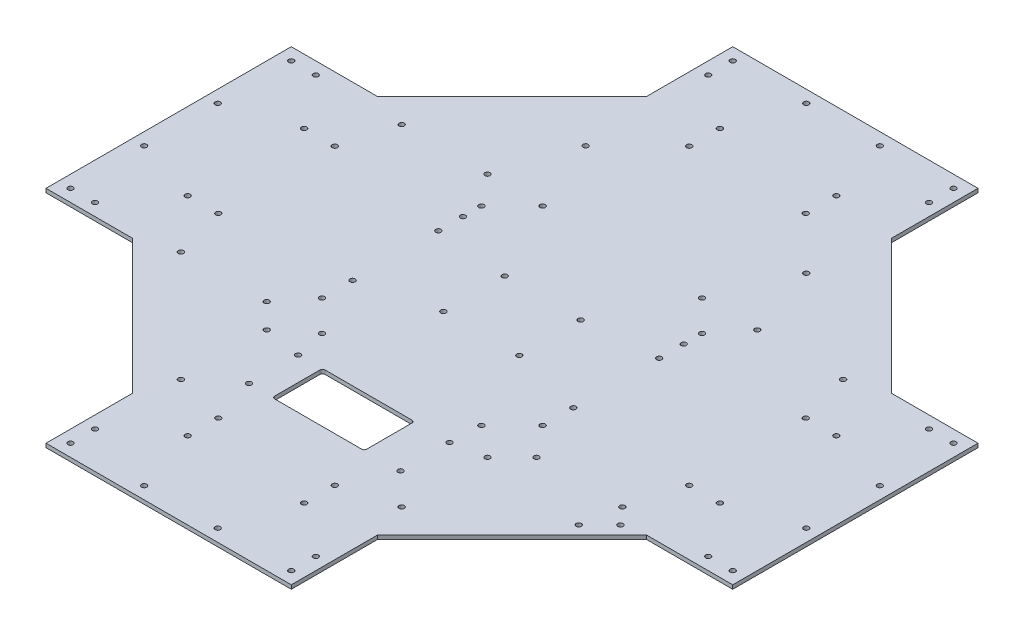
SolidWorks part; units mm, degrees
ref_plane "Front Plane" through (0, 0, 0) normal (0, 0, 1) x (1, 0, 0)
ref_plane "Top Plane" through (0, 0, 0) normal (0, 1, 0) x (1, 0, 0)
ref_plane "Right Plane" through (0, 0, 0) normal (1, 0, 0) x (0, 0, -1)
sketch "Sketch1" plane through (0, 0, 0) normal (0, 1, 0) x (1, 0, 0)
  line L0 (0, -280) -> (100, -280)
  line L1 (100, -280) -> (100, -209.6016)
  line L2 (280, -100) -> (209.6016, -100)
  line L3 (0, 0) -> (0, -280) construction
  line L4 (280, 0) -> (280, -100)
  line L5 (-280, 280) -> (280, 280) construction
  line L6 (-280, 280) -> (-280, -280) construction
  line L7 (-280, -280) -> (280, -280) construction
  line L8 (280, 280) -> (280, -280) construction
  line L9 (-280, 280) -> (280, -280) construction
  line L10 (-280, -280) -> (280, 280) construction
  line L11 (100, -209.6016) -> (209.6016, -100)
  line L12 (-280, 0) -> (-280, -100)
  line L13 (-280, -100) -> (-209.6016, -100)
  line L14 (-209.6016, -100) -> (-100, -209.6016)
  line L15 (-100, -280) -> (-100, -209.6016)
  line L16 (0, -280) -> (-100, -280)
  line L17 (0, 280) -> (-100, 280)
  line L18 (-100, 280) -> (-100, 209.6016)
  line L19 (-100, 209.6016) -> (-209.6016, 100)
  line L20 (-280, 100) -> (-209.6016, 100)
  line L21 (-280, 0) -> (-280, 100)
  line L22 (280, 0) -> (280, 100)
  line L23 (280, 100) -> (209.6016, 100)
  line L24 (209.6016, 100) -> (100, 209.6016)
  line L25 (100, 280) -> (100, 209.6016)
  line L26 (0, 280) -> (100, 280)
  line L27 (111.5258, -219.2889) -> (219.2889, -111.5258) construction
  line L28 (219.2889, -111.5258) -> (247.5732, -139.8101) construction
  line L29 (247.5732, -139.8101) -> (139.8101, -247.5732) construction
  line L30 (139.8101, -247.5732) -> (111.5258, -219.2889) construction
  line L31 (-100, -270) -> (100, -270) construction
  line L32 (-90, -280) -> (-90, 280) construction
  line L33 (-75, -75) -> (75, -75) construction
  line L34 (-75, -75) -> (-75, 75) construction
  line L35 (-75, 75) -> (75, 75) construction
  line L36 (75, -75) -> (75, 75) construction
  line L37 (-75, -75) -> (75, 75) construction
  line L38 (-75, 75) -> (75, -75) construction
  line L39 (-100, -260) -> (100, -260) construction
  line L40 (-280, 40) -> (280, 40) construction
  line L41 (0, 280) -> (0, 0) construction
  line L42 (-280, -90) -> (280, -90) construction
  line L43 (-260, -100) -> (-260, 100) construction
  line L44 (0, 0) -> (-280, 0) construction
  arc A0 (100, -280) -> (280, -100) centre (100, -100) ccw construction
  circle A1 centre (-47.5, -192) radius 2.125
  circle A2 centre (-47.5, -217) radius 2.125
  circle A3 centre (47.5, -217) radius 2.125
  circle A4 centre (47.5, -192) radius 2.125
  circle A5 centre (-192, 47.5) radius 2.125
  circle A6 centre (-217, 47.5) radius 2.125
  circle A7 centre (-192, -47.5) radius 2.125
  circle A8 centre (-217, -47.5) radius 2.125
  circle A9 centre (47.5, 192) radius 2.125
  circle A10 centre (47.5, 217) radius 2.125
  circle A11 centre (-47.5, 192) radius 2.125
  circle A12 centre (-47.5, 217) radius 2.125
  circle A13 centre (192, -47.5) radius 2.125
  circle A14 centre (217, -47.5) radius 2.125
  circle A15 centre (192, 47.5) radius 2.125
  circle A16 centre (217, 47.5) radius 2.125
  circle A17 centre (-90, -270) radius 2.125
  circle A18 centre (-30, -270) radius 2.125
  circle A19 centre (30, -270) radius 2.125
  circle A20 centre (90, -270) radius 2.125
  circle A21 centre (-270, 90) radius 2.125
  circle A22 centre (-270, 30) radius 2.125
  circle A23 centre (-270, -30) radius 2.125
  circle A24 centre (-270, -90) radius 2.125
  circle A25 centre (90, 270) radius 2.125
  circle A26 centre (30, 270) radius 2.125
  circle A27 centre (-30, 270) radius 2.125
  circle A28 centre (-90, 270) radius 2.125
  circle A29 centre (270, -90) radius 2.125
  circle A30 centre (270, -30) radius 2.125
  circle A31 centre (270, 30) radius 2.125
  circle A32 centre (270, 90) radius 2.125
  circle A33 centre (-90, -250) radius 2.125
  circle A34 centre (-90, -180) radius 2.125
  circle A35 centre (-90, -110) radius 2.125
  circle A36 centre (-90, -40) radius 2.125
  circle A37 centre (-90, 30) radius 2.125
  circle A38 centre (-90, 50) radius 2.125
  circle A39 centre (-90, 100) radius 2.125 construction
  circle A40 centre (-90, 150) radius 2.125
  circle A41 centre (-90, 200) radius 2.125 construction
  circle A42 centre (-90, 250) radius 2.125
  circle A43 centre (90, -250) radius 2.125
  circle A44 centre (90, -180) radius 2.125
  circle A45 centre (90, -110) radius 2.125
  circle A46 centre (90, -40) radius 2.125
  circle A47 centre (90, 30) radius 2.125
  circle A48 centre (90, 50) radius 2.125
  circle A49 centre (90, 100) radius 2.125 construction
  circle A50 centre (90, 150) radius 2.125
  circle A51 centre (90, 200) radius 2.125 construction
  circle A52 centre (90, 250) radius 2.125
  circle A53 centre (-250, -90) radius 2.125
  circle A54 centre (-180, -90) radius 2.125
  circle A55 centre (-110, -90) radius 2.125
  circle A56 centre (-110, 90) radius 2.125
  circle A57 centre (-180, 90) radius 2.125
  circle A58 centre (-250, 90) radius 2.125
  circle A59 centre (110, -90) radius 2.125
  circle A60 centre (180, -90) radius 2.125
  circle A61 centre (250, -90) radius 2.125
  circle A62 centre (110, 90) radius 2.125
  circle A63 centre (180, 90) radius 2.125
  circle A64 centre (250, 90) radius 2.125
  point P33 (0, 0)
  point P68 (0, 0)
  point P107 (0, 0)
  dimension "D10" = 25
  dimension "4.25" = 4.25
  dimension "D11" = 4.25
  dimension "D16" = 4.25
  dimension "D24" = 4.25
  dimension "D28" = 4.25
  dimension "D32" = 4.25
  dimension "D1" = 560
  dimension "D2" = 90
  dimension "D3" = 280
  dimension "D4" = 4
  dimension "D5" = 100
  dimension "D6" = 155
  dimension "D7" = 152.4
  dimension "D8" = 15
  dimension "D9" = 40
  dimension "D12" = 47.5
  dimension "D13" = 63
  dimension "D15" = 10
  dimension "D17" = 10
  dimension "D18" = 76.2
  dimension "D19" = 150
  dimension "D20" = 150
  dimension "D23" = 10
  dimension "D25" = 10
  dimension "D26" = 300
  dimension "D29" = 10
  dimension "D31" = 20
  dimension "D33" = 10
  dimension "D21" = 4
  dimension "D27" = 5
  dimension "D30" = 5
  dimension "D34" = 3
  dimension "D14" = 4
  dimension "D22" = 4
extrude "Boss-Extrude1" add sketch "Sketch1" along normal blind 3.175 contours L26 L17 L18 L19 L20 L21 L12 L13 L14 L15 L16 L0 L1 L11 L2 L4 L22 L23 L24 L25 region at (0, 0, -0.0137)
sketch "Sketch2" plane through (0, 3.175, 0) normal (0, 1, 0) x (1, 0, 0)
  line L0 (0, 25.5202) -> (0, -25) construction
  line L1 (-31, -25) -> (31, -25) construction
  line L2 (-31, -25) -> (-31, 25) construction
  line L3 (-31, 25) -> (31, 25) construction
  line L4 (31, -25) -> (31, 25) construction
  line L5 (-31, -25) -> (31, 25) construction
  line L6 (-31, 25) -> (31, -25) construction
  line L7 (75, -75) -> (75, 75) construction
  line L8 (-75, -75) -> (75, -75) construction
  line L9 (-75, -75) -> (-75, 75) construction
  line L10 (-75, 75) -> (75, 75) construction
  line L11 (75, -75) -> (75, 75) construction
  line L12 (-75, -75) -> (75, -75) construction
  line L13 (-75, -75) -> (-75, 75) construction
  line L14 (-75, 75) -> (75, 75) construction
  line L15 (-90, 270) -> (-90, -270) construction
  line L16 (-270, 90) -> (270, 90) construction
  line L17 (-40.0349, -135) -> (34.9651, -135) construction
  line L18 (-40.0349, -155.5) -> (34.9651, -155.5)
  line L19 (-40.0349, -155.5) -> (-40.0349, -114.5)
  line L20 (-40.0349, -114.5) -> (34.9651, -114.5)
  line L21 (34.9651, -155.5) -> (34.9651, -114.5)
  line L22 (-40.0349, -155.5) -> (34.9651, -114.5) construction
  line L23 (-40.0349, -114.5) -> (34.9651, -155.5) construction
  line L26 (92.9289, -202.5305) -> (202.5305, -92.9289)
  line L27 (92.9289, -202.5305) -> (202.5305, -92.9289) construction
  circle A0 centre (-31, 25) radius 2.125
  circle A1 centre (-31, -25) radius 2.125
  circle A2 centre (31, -25) radius 2.125
  circle A3 centre (31, 25) radius 2.125
  circle A4 centre (-90, 65) radius 2.125
  circle A5 centre (-65, 90) radius 2.125
  circle A6 centre (65, 90) radius 2.125
  circle A7 centre (90, 65) radius 2.125
  circle A8 centre (90, -65) radius 2.125
  circle A9 centre (65, -90) radius 2.125
  circle A10 centre (-65, -90) radius 2.125
  circle A11 centre (-90, -65) radius 2.125
  circle A12 centre (64.0651, -115) radius 2.125
  circle A13 centre (64.0651, -155) radius 2.125
  circle A14 centre (-59.4349, -115) radius 2.125
  circle A15 centre (-59.4349, -155) radius 2.125
  circle A16 centre (174.9533, -120.5061) radius 2.125
  circle A17 centre (191.9239, -103.5355) radius 2.125
  point P0 (0, 0)
  point P28 (-2.5349, -135)
  point P43 (0, 0)
  dimension "D3" = 4.25
  dimension "D4" = 4.25
  dimension "D5" = 4.25
  dimension "D7" = 4.25
  dimension "D13" = 4.25
  dimension "D16" = 4.25
  dimension "D20" = 4.25
  dimension "D22" = 4.25
  dimension "D1" = 62
  dimension "D2" = 50
  dimension "D6" = 10
  dimension "D8" = 10
  dimension "D10" = 41
  dimension "D11" = 75
  dimension "D12" = 135
  dimension "D14" = 20
  dimension "D15" = 66.6
  dimension "D17" = 19.4
  dimension "D18" = 20
  dimension "D21" = 116
  dimension "D23" = 24
  dimension "D19" = 10
  dimension "D9" = 4
extrude "Cut-Extrude1" cut sketch "Sketch2" against normal through all
fillet "Fillet1" radius 2 4 edges at (34.9651, 1.5875, 114.5) (34.9651, 1.5875, 155.5) (-40.0349, 1.5875, 155.5) (-40.0349, 1.5875, 114.5)
